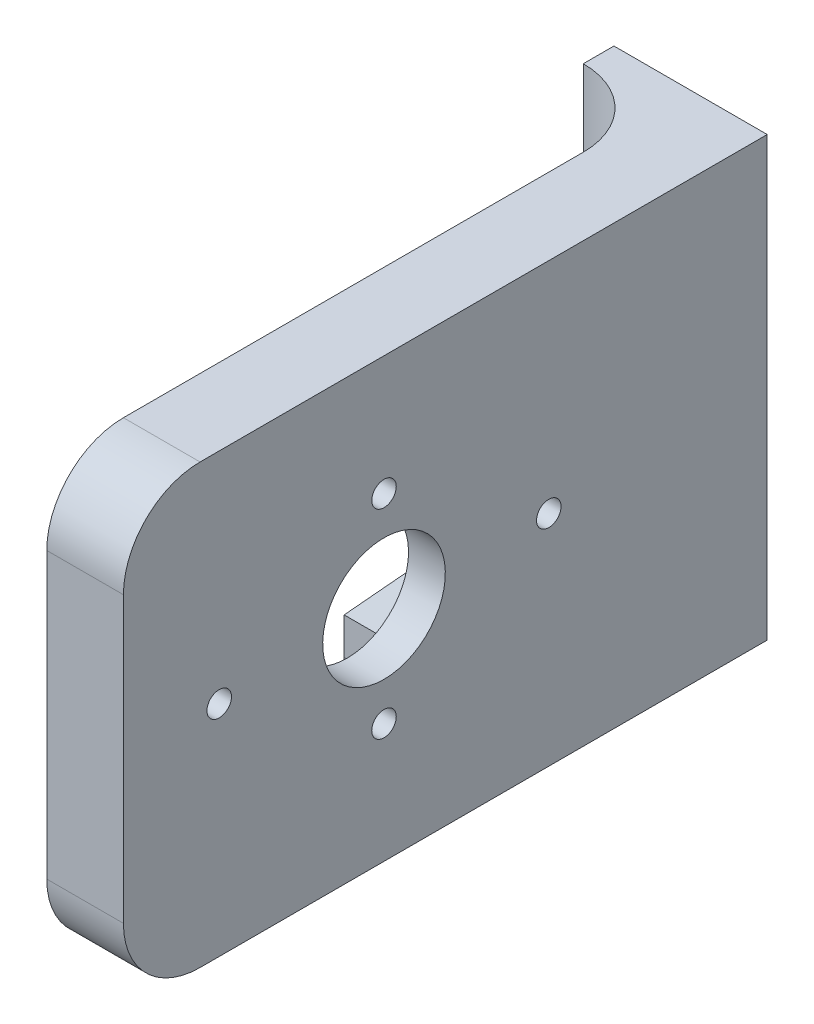
SolidWorks part; units mm, degrees
ref_plane "前视基准面" through (0, 0, 0) normal (0, 0, 1) x (1, 0, 0)
ref_plane "上视基准面" through (0, 0, 0) normal (0, 1, 0) x (1, 0, 0)
ref_plane "右视基准面" through (0, 0, 0) normal (1, 0, 0) x (0, 0, -1)
sketch "草图1" plane through (0, 0, 0) normal (0, 0, 1) x (1, 0, 0)
  line L0 (12.981, 56.4717) -> (12.981, 11.4717)
  line L1 (12.981, 11.4717) -> (17.981, 11.4717)
  line L2 (17.981, 11.4717) -> (17.981, 61.4717)
  line L3 (17.981, 61.4717) -> (12.981, 61.4717)
  line L9 (12.981, 56.4717) -> (12.981, 61.4717)
  dimension "D1" = 90
  dimension "D2" = 5
  dimension "D5" = 50
extrude "凸台-拉伸1" add sketch "草图1" along normal blind 40
fillet "圆角3" radius 6 1 edges at (15.481, 11.4717, 0) type face fillet first side face at (15.481, 11.4717, 20) second side face at (15.481, 36.4717, 0)
fillet "圆角4" radius 6 1 edges at (15.481, 11.4717, 40) type face fillet first side face at (15.481, 36.4717, 40) second side face at (15.481, 11.4717, 23)
sketch "草图2" plane through (12.981, 0, 0) normal (-1, 0, 0) x (0, 0, 1)
  line L10 (25.4, 43.4282) -> (25.4, 40.1179)
  line L11 (37.1158, 39.4558) -> (25.4, 40.1179)
  line L12 (37.1158, 34.5007) -> (25.4, 33.8386)
  line L13 (25.4, 33.8386) -> (25.4, 30.5282)
  line L14 (20.6, 32.9212) -> (20.6, 30.5282)
  line L15 (5.9039, 34.244) -> (20.6, 32.9212)
  line L16 (5.9039, 39.7125) -> (20.6, 41.0352)
  line L17 (20.6, 43.4282) -> (20.6, 41.0352)
  arc A12 (37.1158, 34.5007) -> (37.1158, 39.4558) centre (37.45, 36.9782) ccw
  arc A14 (25.4, 30.5282) -> (20.6, 30.5282) centre (23, 30.5282) cw
  arc A15 (5.9039, 39.7125) -> (5.9039, 34.244) centre (6.15, 36.9782) ccw
  arc A16 (25.4, 43.4282) -> (20.6, 43.4282) centre (23, 43.4282) ccw
  point P17 (21.1, 36.9782)
  point P19 (24.9, 36.9782)
  point P22 (23, 33.5282)
extrude "切除-拉伸1" cut sketch "草图2" against normal blind 2.6
sketch "草图5" plane through (15.581, 0, 0) normal (-1, 0, 0) x (0, 0, 1)
  line L0 (16.55, 36.9782) -> (29.45, 36.9782) construction
  line L1 (23, 22.5282) -> (23, 53.8282) construction
  line L2 (6.15, 36.9782) -> (41.0957, 36.9782) construction
  line L3 (23, 42.794) -> (23, 24.9781) construction
  circle A0 centre (12.25, 36.9782) radius 0.8
  circle A1 centre (23, 36.9782) radius 4
  circle A2 centre (33.75, 36.9782) radius 0.8
  circle A3 centre (23, 30.4782) radius 0.8
  circle A4 centre (23, 43.4782) radius 0.8
  dimension "D1" = 21.5
  dimension "D2" = 13
  dimension "D3" = 8
extrude "切除-拉伸3" cut sketch "草图5" against normal blind 10
ref_plane "基准面1" through (0, 0, 20) normal (0, 0, -1) x (-1, 0, 0)
sketch "草图6" plane through (12.981, 0, 0) normal (-1, 0, 0) x (0, 0, 1)
  line L0 (0, 61.4717) -> (0, 17.4717) construction
  line L1 (46, 22.6958) -> (0, 22.6958)
  line L2 (46, 22.6958) -> (46, 51.2607)
  line L3 (46, 51.2607) -> (0, 51.2607)
  line L4 (0, 22.6958) -> (0, 51.2607)
  line L5 (46, 22.6958) -> (0, 51.2607) construction
  line L6 (46, 51.2607) -> (0, 22.6958) construction
  line L8 (52.8263, 9.7952) -> (-6.8263, 9.7952)
  line L9 (52.8263, 9.7952) -> (52.8263, 64.1613)
  line L10 (52.8263, 64.1613) -> (-6.8263, 64.1613)
  line L11 (-6.8263, 9.7952) -> (-6.8263, 64.1613)
  line L12 (52.8263, 9.7952) -> (-6.8263, 64.1613) construction
  line L13 (52.8263, 64.1613) -> (-6.8263, 9.7952) construction
  point P0 (23, 36.9782)
  point P8 (23, 36.9782)
extrude "切除-拉伸4" cut sketch "草图6" against normal blind 10
sketch "草图7" plane through (0, 0, 0) normal (0, 0, -1) x (-1, 0, 0)
  line L1 (-17.981, 51.2607) -> (-7.981, 51.2607)
  line L2 (-17.981, 51.2607) -> (-17.981, 22.6958)
  line L3 (-17.981, 22.6958) -> (-7.981, 22.6958)
  line L4 (-7.981, 51.2607) -> (-7.981, 22.6958)
  dimension "D1" = 10
extrude "凸台-拉伸2" add sketch "草图7" along normal blind 2
fillet "圆角5" radius 5 3 edges at (15.481, 22.6958, 40) (15.481, 51.2607, 40) (12.981, 36.9782, 0)
